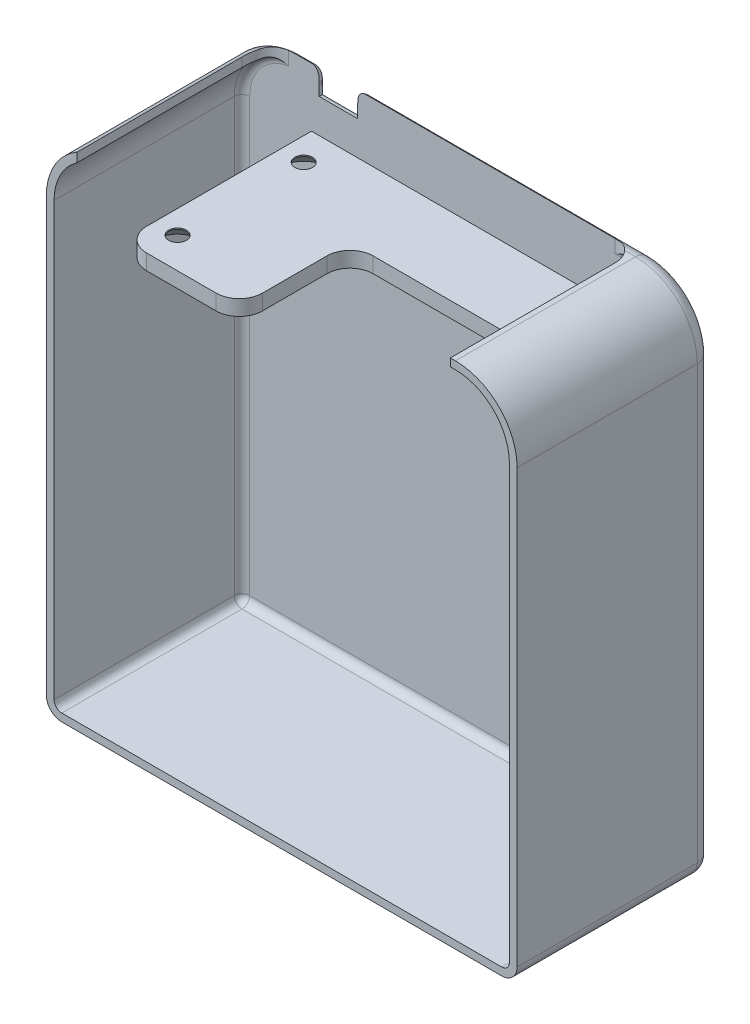
SolidWorks part; units mm, degrees
ref_plane "Front Plane" through (0, 0, 0) normal (0, 0, 1) x (1, 0, 0)
ref_plane "Top Plane" through (0, 0, 0) normal (0, 1, 0) x (1, 0, 0)
ref_plane "Right Plane" through (0, 0, 0) normal (1, 0, 0) x (0, 0, -1)
sketch "Sketch1" plane through (0, 0, 0) normal (0, 0, 1) x (1, 0, 0)
  line L1 (0, 0) -> (61, 0)
  line L2 (0, 0) -> (0, 66.02)
  line L3 (0, 66.02) -> (61, 66.02)
  line L4 (61, 0) -> (61, 66.02)
  dimension "D1" = 66.02
  dimension "D2" = 61
extrude "Boss-Extrude1" add sketch "Sketch1" along normal blind 25.35
fillet "Fillet1" radius 2 6 edges at (0, 0, 12.675) (61, 0, 12.675) (30.5, 0, 0) (61, 33.01, 0) (0, 33.01, 0) (30.5, 66.02, 0)
fillet "Fillet2" radius 8 4 edges at (0.5858, 65.4342, 0.5858) (60.4142, 65.4342, 0.5858) (61, 66.02, 13.675) (0, 66.02, 13.675)
shell "Shell1" thickness 1 removed face at (30.5, 31.8207, 25.35)
sketch "Sketch8" plane through (0, 0, 0) normal (0, 0, -1) x (-1, 0, 0)
  line L0 (-53, 66.02) -> (-8, 66.02) construction
  line L1 (-11, 62.52) -> (-16, 62.52)
  line L2 (-11, 62.52) -> (-11, 66.02)
  line L3 (-11, 66.02) -> (-16, 66.02)
  line L4 (-16, 62.52) -> (-16, 66.02)
  line L5 (0, 58.02) -> (0, 2) construction
  dimension "D1" = 11
  dimension "D2" = 5
  dimension "D3" = 3.5
extrude "Cut-Extrude3" cut sketch "Sketch8" against normal through all
sketch "Sketch2" plane through (0, 0, 25.35) normal (0, 0, 1) x (1, 0, 0)
  line L0 (0, 58.02) -> (0, 2) construction
  line L1 (4, 66.2838) -> (52.35, 66.2838)
  line L2 (4, 66.2838) -> (4, 52.5838)
  line L3 (4, 52.5838) -> (52.35, 52.5838)
  line L4 (52.35, 66.2838) -> (52.35, 52.5838)
  dimension "D1" = 48.35
  dimension "D2" = 13.7
  dimension "D3" = 4
extrude "Cut-Extrude1" cut sketch "Sketch2" against normal blind 24.35
sketch "Sketch3" plane through (0, 0, 1) normal (0, 0, 1) x (1, 0, 0)
  line L0 (2, 1) -> (59, 1) construction
  line L1 (10, 58.12) -> (51, 58.12)
  line L2 (10, 58.12) -> (10, 56.12)
  line L3 (10, 56.12) -> (51, 56.12)
  line L4 (51, 58.12) -> (51, 56.12)
  line L5 (54, 1) -> (53, 1)
  line L6 (54, 1) -> (54, 38.5)
  line L7 (54, 38.5) -> (53, 38.5)
  line L8 (53, 1) -> (53, 38.5)
  line L9 (53, 66.02) -> (52.35, 66.02) construction
  line L10 (0, 58.02) -> (0, 2) construction
  line L11 (61, 2) -> (61, 58.02) construction
  dimension "D1" = 2
  dimension "D2" = 1
  dimension "D3" = 7.9
  dimension "D4" = 10
  dimension "D5" = 10
  dimension "D6" = 7
  dimension "D7" = 37.5
extrude "Boss-Extrude2" add sketch "Sketch3" along normal blind 10
sketch "Sketch4" plane through (0, 0, 11) normal (0, 0, 1) x (1, 0, 0)
  line L0 (10, 56.12) -> (51, 56.12) construction
  line L1 (10, 58.12) -> (25, 58.12)
  line L2 (10, 58.12) -> (10, 56.12)
  line L3 (10, 56.12) -> (25, 56.12)
  line L4 (25, 58.12) -> (25, 56.12)
  dimension "D1" = 15
extrude "Boss-Extrude3" add sketch "Sketch4" along normal blind 14.35
sketch "Sketch5" plane through (54, 0, 0) normal (1, 0, 0) x (0, 0, -1)
  line L0 (-1, 31.6) -> (-1, 38.6)
  line L1 (-1, 38.6) -> (-4.2, 38.6)
  line L2 (-1, 31.6) -> (-4.2, 31.6)
  line L3 (-11, 1) -> (-2, 1) construction
  line L4 (-1, 58.02) -> (-1, 2) construction
  arc A0 (-4.2, 38.6) -> (-4.2, 31.6) centre (-4.2, 35.1) ccw
  dimension "D1" = 7
  dimension "D2" = 3.2
  dimension "D3" = 34.1
extrude "Boss-Extrude4" add sketch "Sketch5" along normal blind 6
sketch "Sketch6" plane through (0, 56.12, 0) normal (0, -1, 0) x (1, 0, 0)
  line L0 (13, 1) -> (13, 25.35) construction
  line L1 (10, 1) -> (51, 1) construction
  line L2 (10, 25.35) -> (25, 25.35) construction
  line L3 (10, 25.35) -> (10, 1) construction
  circle A0 centre (13, 21.35) radius 1.15
  circle A1 centre (13, 5) radius 1.15
  dimension "D2" = 2.3
  dimension "D1" = 3
  dimension "D3" = 4
  dimension "D4" = 4
extrude "Cut-Extrude2" cut sketch "Sketch6" against normal blind 6
chamfer "Chamfer1" distance 1.85 2 edges at (13, 56.12, 3.85) (13, 56.12, 20.2)
fillet "Fillet3" radius 1 5 edges at (11, 65.02, 0.2679) (16, 65.02, 0.2679) (11, 63.27, 0) (13.5, 62.52, 0) (16, 63.27, 0)
fillet "Fillet4" radius 3 6 edges at (53.5, 1, 11) (53.5, 38.5, 11) (51, 57.12, 11) (25, 57.12, 25.35) (10, 57.12, 25.35)
fillet "Fillet5" radius 3 2 edges at (52.35, 64.886, 1) (4, 63.5646, 1)
